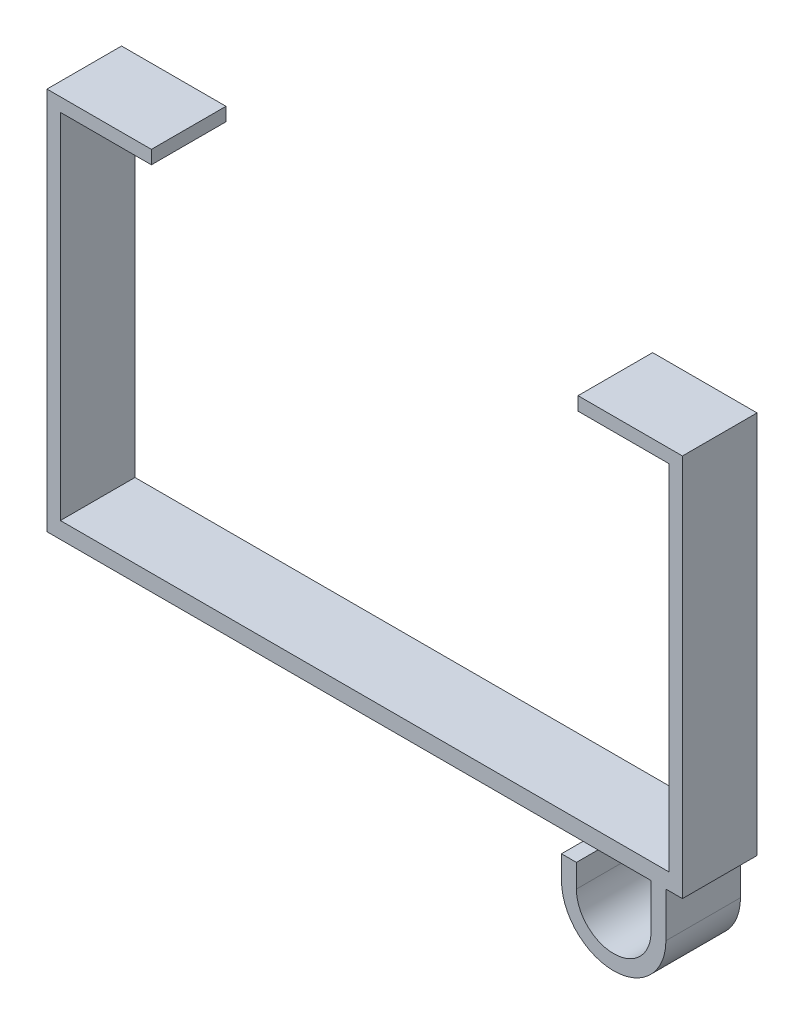
SolidWorks part; units mm, degrees
ref_plane "Front Plane" through (0, 0, 0) normal (0, 0, 1) x (1, 0, 0)
ref_plane "Top Plane" through (0, 0, 0) normal (0, 1, 0) x (1, 0, 0)
ref_plane "Right Plane" through (0, 0, 0) normal (1, 0, 0) x (0, 0, -1)
sketch "Sketch1" plane through (0, 0, 0) normal (0, 0, 1) x (1, 0, 0)
  line L0 (-14.3, 11.95) -> (-14.3, 12.85)
  line L1 (-21.3, 12.85) -> (-14.3, 12.85)
  line L2 (-21.3, 12.85) -> (-21.3, -12.85)
  line L3 (-21.3, -12.85) -> (21.3, -12.85)
  line L4 (21.3, 12.85) -> (21.3, -12.85)
  line L5 (0, -12.85) -> (0, -11.75) construction
  line L6 (-21.3, 0) -> (-20.4, 0) construction
  line L7 (-20.4, 11.95) -> (-14.3, 11.95)
  line L8 (-20.4, 11.95) -> (-20.4, -11.75)
  line L9 (-20.4, -11.75) -> (20.4, -11.75)
  line L10 (20.4, 11.95) -> (20.4, -11.75)
  line L11 (20.4, 0) -> (21.3, 0) construction
  line L12 (13.1907, -12.85) -> (13.1907, -15.85)
  line L13 (14.3, 12.85) -> (14.3, 11.95)
  line L14 (14.3, 12.85) -> (21.3, 12.85)
  line L15 (14.3, 11.95) -> (20.4, 11.95)
  line L16 (20.1907, -15.85) -> (19.1907, -15.85)
  line L17 (14.1907, -15.85) -> (14.1907, -12.85)
  line L18 (19.1907, -15.85) -> (19.1907, -12.85)
  line L19 (19.1907, -12.85) -> (20.1907, -12.85)
  line L20 (20.1907, -12.85) -> (20.1907, -15.85)
  line L21 (13.1907, -14.2995) -> (14.1907, -14.2995)
  arc A0 (13.1907, -15.85) -> (20.1907, -15.85) centre (16.6907, -15.85) ccw
  arc A1 (19.1907, -15.85) -> (14.1907, -15.85) centre (16.6907, -15.85) cw
  point P0 (0, 0)
  point P4 (0, 0)
  point P29 (0, 0)
  point P30 (0, 0)
  dimension "D7" = 1
  dimension "D8" = 0
  dimension "D10" = 2.5
  dimension "D11" = 3.5
  dimension "D1" = 25.7
  dimension "D2" = 42.6
  dimension "D3" = 23.7
  dimension "D4" = 40.8
  dimension "D5" = 7
  dimension "D6" = 7
  dimension "D9" = 1
  dimension "D12" = 3
  dimension "D13" = 0
  dimension "D14" = 0
  dimension "D15" = 1.4495
extrude "Boss-Extrude1" add sketch "Sketch1" along normal blind 5 contours L13 L15 L10 L9 L8 L7 L0 L1 L2 L3 L4 L14 region at (-17.35, 12.4475, 0)
extrude "Boss-Extrude2" add sketch "Sketch1<3>" along normal blind 5 contours L16 A1 L17 L3 L12 A0 | L20 L19 L18 L16 region at (13.6907, -14.3859, 0) region at (19.6907, -14.35, 0)
sketch "Sketch1<3>" plane through (0, 0, 0) normal (0, 0, 1) x (1, 0, 0) same geometry as "Sketch1"
